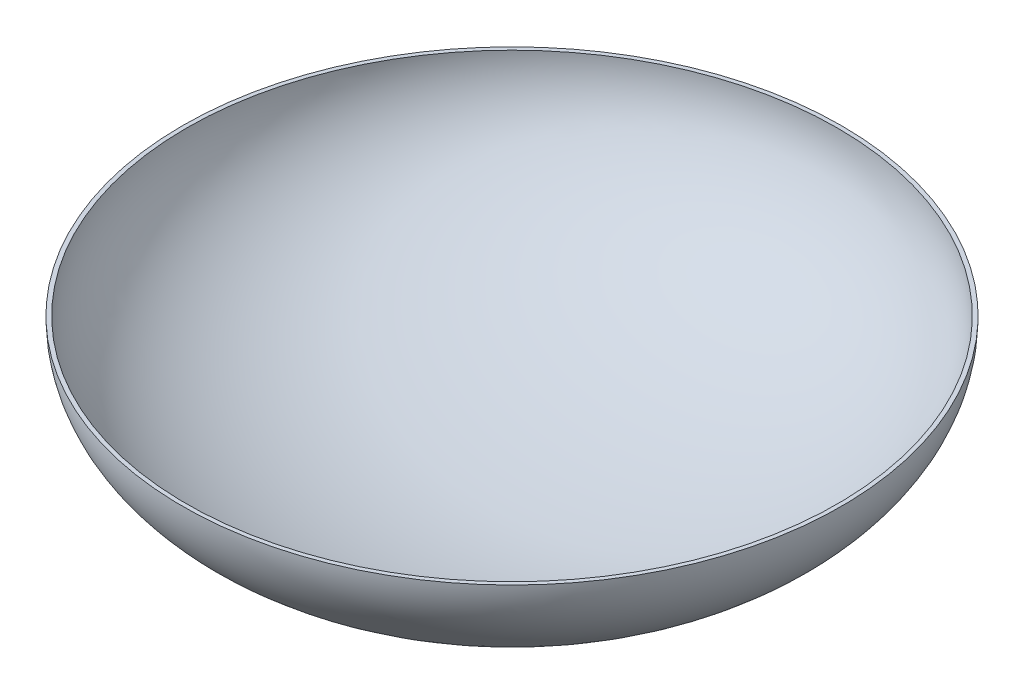
SolidWorks part; units mm, degrees
ref_plane "Front Plane" through (0, 0, 0) normal (0, 0, 1) x (1, 0, 0)
ref_plane "Top Plane" through (0, 0, 0) normal (0, 1, 0) x (1, 0, 0)
ref_plane "Right Plane" through (0, 0, 0) normal (1, 0, 0) x (0, 0, -1)
sketch "Sketch1" plane through (0, 0, 0) normal (0, 0, 1) x (1, 0, 0)
  line L0 (0, 50.8) -> (-101.6, 50.8) construction
  line L1 (0, 0) -> (0, -1.27)
  line L2 (-101.6, 50.8) -> (-102.87, 50.8)
  line L3 (0, 50.8) -> (0, 93.1589) construction
  ellipse E0 centre (0, 50.8) end of major axis (101.6, 50.8) minor radius 50.8 (-101.6, 50.8) -> (0, 0) ccw
  spline S1 degree 3 poles (-102.87, 50.8) (-102.87, 47.31) (-101.4886, 40.3299) (-93.4399, 27.0905) (-74.2605, 12.7788) (-40.1422, 1.3903) (-13.3807, -1.27) (0, -1.27) knots 3.141593 3.141593 3.141593 3.141593 3.337942 3.534292 3.926991 4.31969 4.712389 4.712389 4.712389 4.712389
  dimension "D1" = 101.6
  dimension "D2" = 50.8
revolve "Revolve1" add sketch "Sketch1" angle 360 about L3
